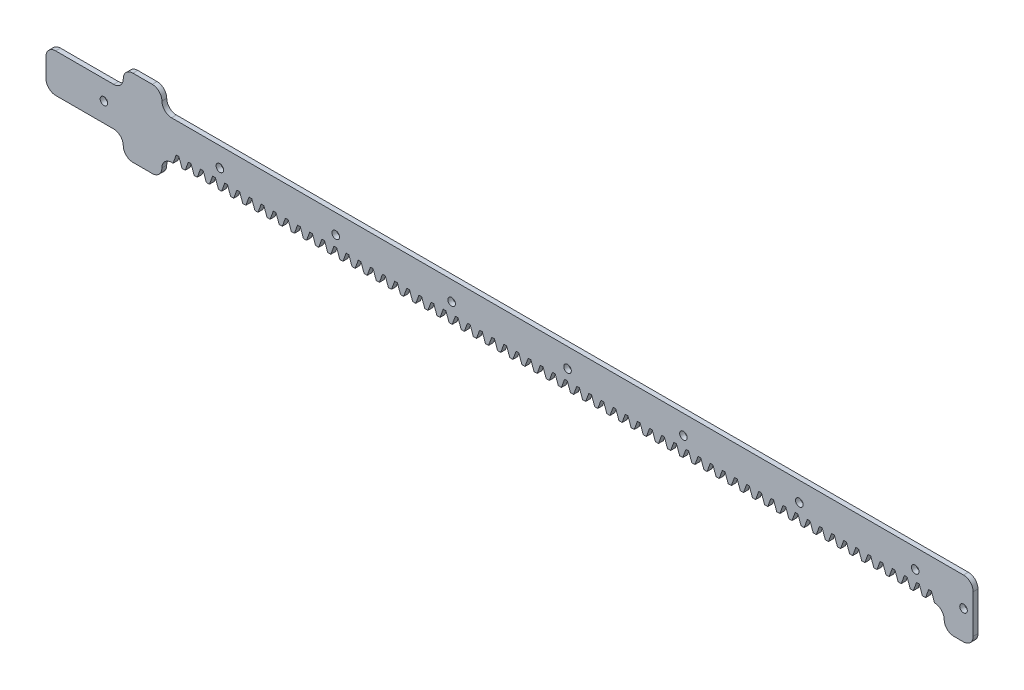
SolidWorks part; units mm, degrees
material "PC High Viscosity"
ref_plane "Front Plane" through (0, 0, 0) normal (0, 0, 1) x (1, 0, 0)
ref_plane "Top Plane" through (0, 0, 0) normal (0, 1, 0) x (1, 0, 0)
ref_plane "Right Plane" through (0, 0, 0) normal (1, 0, 0) x (0, 0, -1)
sketch "Sketch1" plane through (0, 0, 0) normal (0, 0, 1) x (1, 0, 0)
  line L0 (50.8, 0) -> (50.8, -12.7)
  line L1 (0, 0) -> (590.55, 0)
  line L2 (0, 0) -> (0, 25.4)
  line L3 (0, 25.4) -> (609.6, 25.4)
  line L4 (609.6, 0) -> (609.6, 25.4)
  line L5 (50.8, 38.1) -> (76.2, 38.1)
  line L6 (76.2, 38.1) -> (76.2, 25.4)
  line L7 (50.8, 38.1) -> (50.8, 25.4)
  line L8 (76.2, 0) -> (76.2, -12.7)
  line L9 (76.2, -12.7) -> (50.8, -12.7)
  line L10 (590.55, 0) -> (590.55, -12.7)
  line L11 (609.6, 10.0162) -> (603.25, 13.6823) construction
  line L12 (603.25, 13.6823) -> (596.9, 10.0162) construction
  line L13 (596.9, 10.0162) -> (596.9, 2.6838) construction
  line L14 (596.9, 2.6838) -> (603.25, -0.9823) construction
  line L15 (603.25, -0.9823) -> (609.6, 2.6838) construction
  line L16 (609.6, 2.6838) -> (609.6, 10.0162) construction
  line L17 (609.6, 0) -> (609.6, -12.7)
  line L18 (609.6, -12.7) -> (590.55, -12.7)
  circle A0 centre (603.25, 6.35) radius 2.4892
  circle A1 centre (603.25, 6.35) radius 6.35 construction
  dimension "D5" = 4.9784
  dimension "D6" = 12.7
  dimension "D7" = 12.7
  dimension "D1" = 609.6
  dimension "D2" = 25.4
  dimension "D3" = 25.4
  dimension "D4" = 50.8
  dimension "D8" = 19.05
  dimension "D9" = 12.7
extrude "Boss-Extrude1" add sketch "Sketch1" along normal blind 3.175 contours L6 L5 L3 | L1 L4 L3 L2 A0 | L9 L8 L1 region at (63.5, -6.35, 0) region at (308.9784, 12.4144, 0) region at (63.5, 31.75, 0)
fillet "Fillet2" radius 6.35 14 edges at (76.2, 38.1, 1.5875) (76.2, 25.4, 1.5875) (609.6, 25.4, 1.5875) (76.2, 0, 1.5875) (76.2, -12.7, 1.5875) (50.8, -12.7, 1.5875) (50.8, 0, 1.5875) (0, 0, 1.5875) (50.8, 38.1, 1.5875) (50.8, 25.4, 1.5875) (0, 25.4, 1.5875) (590.55, 0, 1.5875) (590.55, -12.7, 1.5875) (609.6, -12.7, 1.5875)
sketch "Sketch2" plane through (0, 0, 3.175) normal (0, 0, 1) x (1, 0, 0)
  line L0 (584.2, 0) -> (82.55, 0)
  line L1 (82.55, 0) -> (82.55, 5.715)
  line L2 (82.55, 5.715) -> (584.2, 5.715)
  line L3 (584.2, 5.715) -> (584.2, 0)
  line L5 (583.2755, 2.54) -> (575.111, 2.54) construction
  line L6 (584.2, 0) -> (582.1199, 5.715)
  line L7 (82.55, 0) -> (584.2, 0) construction
  line L8 (578.2688, 0) -> (584.2, 0)
  line L9 (579.389, 0) -> (584.2, 0)
  line L10 (582.1199, 5.715) -> (580.3488, 5.715)
  line L11 (584.2, 0) -> (578.2688, 0)
  line L12 (578.2688, 0) -> (580.3488, 5.715)
  line L13 (580.3488, 5.715) -> (582.1199, 5.715)
  line L14 (584.2, 0) -> (578.2688, 0)
  line L15 (580.3488, 5.715) -> (582.1199, 5.715)
  line L16 (584.2, 0) -> (578.2688, 0)
  line L17 (578.2688, 0) -> (576.0355, 0)
  line L19 (582.1199, 5.715) -> (580.3488, 5.715) construction
  line L20 (578.2688, 0) -> (576.0355, 0) construction
  point P8 (579.1932, 2.54)
  point P16 (583.2755, 2.54)
  point P17 (575.111, 2.54)
  dimension "D1" = 70
  dimension "D2" = 2.54
  dimension "D3" = 3.175
  dimension "D4" = 70
  dimension "D5" = 1.7711
extrude "Cut-Extrude1" cut sketch "Sketch2" against normal through all contours L12 L0 L8 L6 L2 region at (581.2344, 2.343, 3.175)
pattern_linear "LPattern1" count 63 spacing 7.9796 along (-1, 0, 0) of "Cut-Extrude1"
sketch "Sketch3" plane through (0, 0, 3.175) normal (0, 0, 1) x (1, 0, 0)
  line L0 (82.55, 25.4) -> (603.25, 25.4) construction
  line L1 (609.6, 19.05) -> (609.6, -6.35) construction
  circle A0 centre (571.5, 12.7) radius 2.4892
  point P18 (492.7097, 12.7)
  point P23 (0, 0)
  point P24 (0, 0)
  dimension "D2" = 4.9784
  dimension "D4" = 12.7
  dimension "D5" = 38.1
extrude "Cut-Extrude2" cut sketch "Sketch3" against normal through all
pattern_linear "LPattern2" count 8 spacing 76.2 along (-1, 0, 0) of "Cut-Extrude2"
